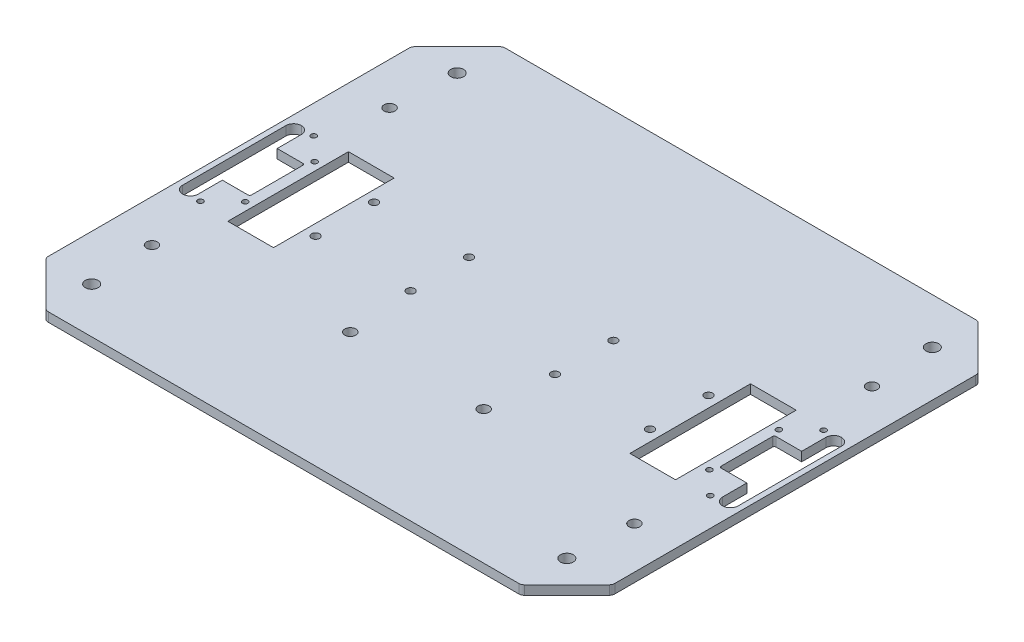
SolidWorks part; units mm, degrees
ref_plane "Plan de face" through (0, 0, 0) normal (0, 0, 1) x (1, 0, 0)
ref_plane "Plan de dessus" through (0, 0, 0) normal (0, 1, 0) x (1, 0, 0)
ref_plane "Plan de droite" through (0, 0, 0) normal (1, 0, 0) x (0, 0, -1)
sketch "Esquisse1" plane through (0, 0, 0) normal (0, 1, 0) x (1, 0, 0)
  line L0 (0, 125) -> (0, -125) construction
  line L1 (-155, 0) -> (155, 0) construction
  line L2 (-130, 125) -> (130, 125)
  line L3 (-130, -125) -> (130, -125)
  line L4 (-155, 100) -> (-155, -100)
  line L5 (155, 100) -> (155, -100)
  line L6 (-155, 100) -> (-130, 125)
  line L7 (-155, -100) -> (-130, -125)
  line L8 (130, -125) -> (155, -100)
  line L9 (130, 125) -> (155, 100)
  point P4 (0, 0)
  point P8 (0, 0)
  point P10 (0, 125)
  point P14 (0, -125)
  point P17 (-155, 0)
  point P20 (155, 0)
  dimension "D1" = 310
  dimension "D2" = 250
  dimension "D3" = 135
  dimension "D4" = 260
  dimension "D5" = 200
extrude "Boss.-Extru.1" add sketch "Esquisse1" along normal blind 5
fillet "Congé1" radius 3 8 edges at (-155, 2.5, 100) (-130, 2.5, 125) (130, 2.5, 125) (155, 2.5, 100) (155, 2.5, -100) (130, 2.5, -125) (-130, 2.5, -125) (-155, 2.5, -100)
sketch "Esquisse2" plane through (0, 5, 0) normal (0, 1, 0) x (1, 0, 0)
  line L0 (155, 0) -> (-155, 0) construction
  line L1 (-155, 98.7574) -> (-155, -98.7574) construction
  line L2 (-132, 0) -> (-132, -65) construction
  line L3 (-132, -65) -> (-155, -65) construction
  line L4 (0, 125) -> (0, -125) construction
  line L5 (-128.7574, -125) -> (128.7574, -125) construction
  circle A0 centre (-132, -65) radius 3
  circle A1 centre (-132, 65) radius 3
  circle A2 centre (132, -65) radius 3
  circle A3 centre (132, 65) radius 3
  point P6 (0, 0)
  point P18 (0, 0)
  dimension "D3" = 6
  dimension "D1" = 23
  dimension "D2" = 65
extrude "Perçage Profilé" cut sketch "Esquisse2" against normal through all
sketch "Esquisse3" plane through (0, 5, 0) normal (0, 1, 0) x (1, 0, 0)
  line L0 (-127, 19) -> (-127, -19) construction
  line L1 (155, 0) -> (-155, 0) construction
  line L2 (-155, 98.7574) -> (-155, -98.7574) construction
  line L3 (0, 125) -> (0, -125) construction
  line L4 (-128.7574, -125) -> (128.7574, -125) construction
  line L5 (-139.5, -31) -> (-139.5, 31) construction
  circle A0 centre (-127, 19) radius 1.5
  circle A1 centre (-127, -19) radius 1.5
  circle A2 centre (127, -19) radius 1.5
  circle A3 centre (127, 19) radius 1.5
  circle A4 centre (-139.5, 31) radius 1.5
  circle A5 centre (-139.5, -31) radius 1.5
  circle A6 centre (139.5, -31) radius 1.5
  circle A7 centre (139.5, 31) radius 1.5
  point P4 (-127, 0)
  point P10 (0, 0)
  point P16 (0, 0)
  point P23 (-139.5, 0)
  dimension "D2" = 3
  dimension "D1" = 38
  dimension "D3" = 28
  dimension "D4" = 62
  dimension "D5" = 12.5
extrude "Perçage Encodeur" cut sketch "Esquisse3" against normal through all
sketch "Esquisse4" plane through (0, 5, 0) normal (0, 1, 0) x (1, 0, 0)
  line L0 (155, 0) -> (-155, 0) construction
  line L1 (143.5, -15) -> (129.5, -15)
  line L2 (-128.5, -14) -> (-128.5, 14)
  line L4 (-129.5, 15) -> (-143.5, 15)
  line L5 (-143.5, 15) -> (-143.5, 32.5)
  line L6 (-143.5, 32.5) -> (-152, 32.5)
  line L7 (-152, 32.5) -> (-152, -32.5)
  line L8 (-152, -32.5) -> (-143.5, -32.5)
  line L9 (-143.5, -32.5) -> (-143.5, -15)
  line L10 (-143.5, -15) -> (-129.5, -15)
  line L12 (-143.5, 15) -> (-143.5, -15) construction
  line L13 (143.5, -32.5) -> (143.5, -15)
  line L14 (0, 125) -> (0, -125) construction
  line L15 (-128.7574, -125) -> (128.7574, -125) construction
  line L16 (152, -32.5) -> (143.5, -32.5)
  line L27 (-155, 98.7574) -> (-155, -98.7574) construction
  line L28 (152, 32.5) -> (152, -32.5)
  line L29 (143.5, 32.5) -> (152, 32.5)
  line L30 (143.5, 15) -> (143.5, 32.5)
  line L31 (129.5, 15) -> (143.5, 15)
  line L32 (128.5, -14) -> (128.5, 14)
  arc A0 (-128.5, -14) -> (-129.5, -15) centre (-129.5, -14) cw
  arc A1 (-128.5, 14) -> (-129.5, 15) centre (-129.5, 14) ccw
  arc A2 (128.5, 14) -> (129.5, 15) centre (129.5, 14) cw
  arc A3 (128.5, -14) -> (129.5, -15) centre (129.5, -14) ccw
  point P6 (0, 0)
  point P10 (-128.5, 0)
  point P19 (-143.5, 0)
  point P25 (0, 0)
  point P28 (-128.5, 15)
  point P32 (-152, 0)
  point P45 (128.5, 15)
  point P46 (128.5, 0)
  dimension "D2" = 1
  dimension "D1" = 15
  dimension "D3" = 8.5
  dimension "D4" = 65
  dimension "D5" = 30
  dimension "D6" = 3
extrude "Poche Roue Encodeuse" cut sketch "Esquisse4" against normal through all
fillet "Congé2" radius 4.25 4 edges at (152, 2.5, 32.5) (152, 2.5, -32.5) (-152, 2.5, 32.5) (-152, 2.5, -32.5)
fillet "Congé3" radius 4.25 4 edges at (143.5, 2.5, 32.5) (143.5, 2.5, -32.5) (-143.5, 2.5, 32.5) (-143.5, 2.5, -32.5)
sketch "Esquisse5" plane through (0, 5, 0) normal (0, 1, 0) x (1, 0, 0)
  line L0 (0, 125) -> (0, -125) construction
  line L1 (128.7574, 125) -> (-128.7574, 125) construction
  line L2 (-128.7574, -125) -> (128.7574, -125) construction
  line L3 (-155, 0) -> (155, 0) construction
  line L4 (-155, 98.7574) -> (-155, -98.7574) construction
  line L5 (155, -98.7574) -> (155, 98.7574) construction
  line L7 (-39.5, 16) -> (-91.5, 16) construction
  line L8 (-39.5, 16) -> (-39.5, -16) construction
  line L9 (-39.5, -16) -> (-91.5, -16) construction
  line L10 (-91.5, 16) -> (-91.5, -16) construction
  circle A0 centre (-91.5, 16) radius 2.2
  circle A1 centre (-91.5, -16) radius 2.2
  circle A2 centre (-39.5, -16) radius 2.2
  circle A3 centre (-39.5, 16) radius 2.2
  circle A4 centre (39.5, 16) radius 2.2
  circle A5 centre (39.5, -16) radius 2.2
  circle A6 centre (91.5, -16) radius 2.2
  circle A7 centre (91.5, 16) radius 2.2
  point P16 (-39.5, 0)
  dimension "D4" = 4.4
  dimension "D1" = 32
  dimension "D2" = 52
  dimension "D3" = 91.5
extrude "Perçage Bloc Moteur" cut sketch "Esquisse5" against normal through all
sketch "Esquisse6" plane through (0, 5, 0) normal (0, 1, 0) x (1, 0, 0)
  line L0 (-91.5, 16) -> (-91.5, -16) construction
  line L1 (-122.5, 33) -> (-97.5, 33)
  line L2 (-122.5, 33) -> (-122.5, -33)
  line L3 (-122.5, -33) -> (-97.5, -33)
  line L4 (-97.5, 33) -> (-97.5, -33)
  line L5 (-97.5, 0) -> (-91.5, 0) construction
  line L6 (0, 125) -> (0, -125) construction
  line L7 (-128.7574, -125) -> (128.7574, -125) construction
  line L8 (122.5, -33) -> (97.5, -33)
  line L9 (97.5, 33) -> (97.5, -33)
  line L10 (122.5, 33) -> (122.5, -33)
  line L11 (122.5, 33) -> (97.5, 33)
  point P16 (0, 0)
  dimension "D1" = 25
  dimension "D2" = 6
  dimension "D3" = 66
extrude "Poche Roue Motrice" cut sketch "Esquisse6" against normal through all
sketch "Esquisse7" plane through (0, 5, 0) normal (0, 1, 0) x (1, 0, 0)
  line L0 (-155, 98.7574) -> (-155, -98.7574) construction
  line L1 (128.7574, 125) -> (-128.7574, 125) construction
  line L2 (0, 125) -> (0, -125) construction
  line L3 (-128.7574, -125) -> (128.7574, -125) construction
  line L4 (-155, 0) -> (155, 0) construction
  line L5 (155, -98.7574) -> (155, 98.7574) construction
  circle A0 centre (-130, 100) radius 3.5
  circle A1 centre (-130, -100) radius 3.5
  circle A2 centre (130, -100) radius 3.5
  circle A3 centre (130, 100) radius 3.5
  point P12 (0, 0)
  point P18 (0, 0)
  dimension "D1" = 7
  dimension "D2" = 25
  dimension "D3" = 25
extrude "Perçage Patin" cut sketch "Esquisse7" against normal through all
sketch "Esquisse8" plane through (0, 5, 0) normal (0, 1, 0) x (1, 0, 0)
  line L0 (0, -125) -> (0, -52) construction
  line L1 (-128.7574, -125) -> (128.7574, -125) construction
  line L2 (36.5, -52) -> (-36.5, -52) construction
  circle A0 centre (-36.5, -52) radius 3
  circle A1 centre (36.5, -52) radius 3
  point P8 (0, -52)
  dimension "D3" = 6
  dimension "D1" = 73
  dimension "D2" = 73
extrude "Enlèv. mat.-Extru.1" cut sketch "Esquisse8" against normal through all
